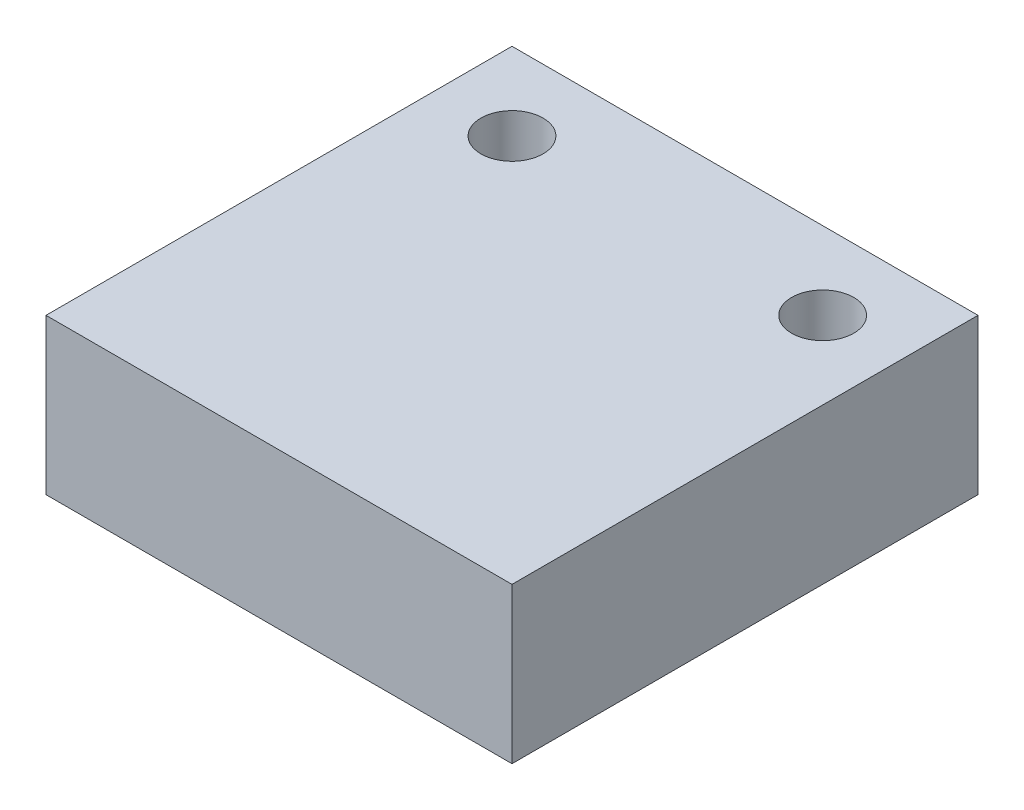
SolidWorks part; units mm, degrees
ref_plane "Front Plane" through (0, 0, 0) normal (0, 0, 1) x (1, 0, 0)
ref_plane "Top Plane" through (0, 0, 0) normal (0, 1, 0) x (1, 0, 0)
ref_plane "Right Plane" through (0, 0, 0) normal (1, 0, 0) x (0, 0, -1)
other "Center of Mass"
sketch "Sketch1" plane through (0, 0, 0) normal (0, 1, 0) x (1, 0, 0)
  line L1 (-75, 75) -> (75, 75)
  line L2 (-75, 75) -> (-75, -75)
  line L3 (-75, -75) -> (75, -75)
  line L4 (75, 75) -> (75, -75)
  line L5 (-75, 75) -> (75, -75) construction
  line L6 (-75, -75) -> (75, 75) construction
  point P0 (0, 0)
  dimension "D1" = 150
  dimension "D2" = 150
extrude "Boss-Extrude1" add sketch "Sketch1" along normal blind 50
sketch "Sketch2" plane through (0, 50, 0) normal (0, 1, 0) x (1, 0, 0)
  line L1 (0, -27.5) -> (0, 27.5) construction
  circle A0 centre (-50, 50) radius 10
  circle A3 centre (50, 50) radius 10
  dimension "D1" = 20
  dimension "D2" = 50
  dimension "D3" = 50
extrude "Cut-Extrude1" cut sketch "Sketch2" against normal blind 50
ref_plane "Plane4" through (0, 0, 0) normal (0, 0, -1) x (-1, 0, 0)
ref_plane "Plane5" through (0, 0, 0) normal (-1, 0, 0) x (0, 0, 1)
ref_axis "EE" through (0, -3.4889, 0) along (0, 1, 0)
